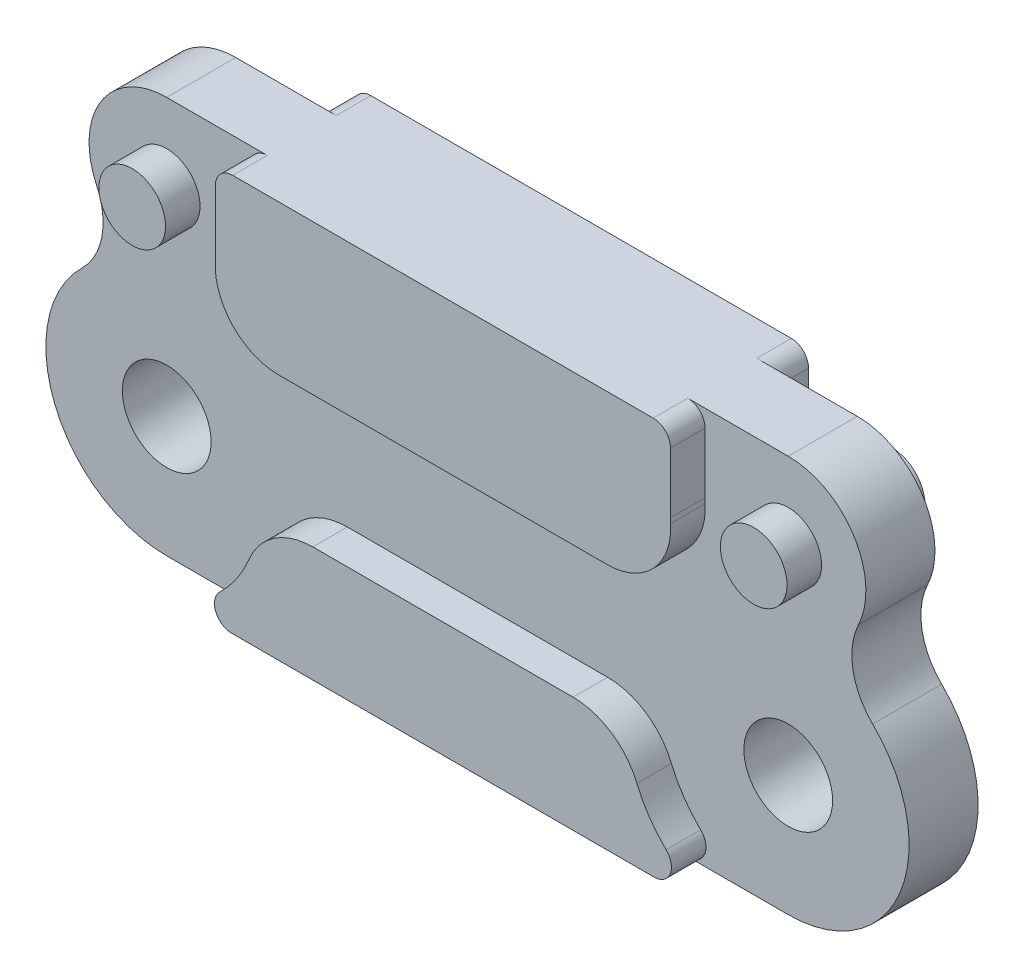
SolidWorks part; units mm, degrees
material "ABS"
ref_plane "Front Plane" through (0, 0, 0) normal (0, 0, 1) x (1, 0, 0)
ref_plane "Top Plane" through (0, 0, 0) normal (0, 1, 0) x (1, 0, 0)
ref_plane "Right Plane" through (0, 0, 0) normal (1, 0, 0) x (0, 0, -1)
sketch "Sketch1" plane through (0, 0, 0) normal (0, 0, 1) x (1, 0, 0)
  line L0 (0, 0) -> (-14.2875, 0)
  line L1 (-14.2875, 5.5563) -> (0, 5.5563)
  line L2 (0, 5.5563) -> (0, 0)
  circle A0 centre (-14.2875, 0) radius 1.7859
  circle A1 centre (-14.2875, 0) radius 5.5563
  circle A2 centre (-14.2875, 9.1281) radius 3.5719
  circle A3 centre (-14.2875, 9.1281) radius 1.7859
  circle A4 centre (-20.388, 6.2465) radius 3.175
  circle A5 centre (-7.5523, 8.7312) radius 3.175
  circle A6 centre (-1.2023, 8.7312) radius 3.175 construction
  circle A7 centre (-7.5523, 8.7312) radius 1.7859 construction
  dimension "D2" = 3.5719
  dimension "D3" = 11.1125
  dimension "D4" = 7.1437
  dimension "D5" = 6.35
  dimension "D1" = 14.2875
sketch "Sketch2" plane through (0, 0, 0) normal (0, 0, 1) x (1, 0, 0)
  line L0 (-7.5523, 11.9062) -> (7.5523, 11.9062)
  line L1 (-14.2875, -5.5563) -> (14.2875, -5.5563)
  line L2 (0, 12.7) -> (0, 15.1901) construction
  line L3 (-10.3989, -3.9688) -> (10.3989, -3.9688)
  line L4 (-14.2875, 12.7) -> (0, 12.7)
  line L5 (0, 12.7) -> (14.2875, 12.7)
  circle A0 centre (-14.2875, 0) radius 5.5563
  circle A12 centre (-14.2875, 0) radius 2.0399
  circle A14 centre (-14.2875, 0) radius 1.7859 construction
  circle A16 centre (-7.5523, 8.7312) radius 3.175
  circle A18 centre (-7.5523, 8.7312) radius 3.175 construction
  circle A19 centre (-20.388, 6.2465) radius 3.175
  circle A20 centre (-14.2875, 9.1281) radius 3.5719
  circle A21 centre (-14.2875, 9.1281) radius 3.5719 construction
  circle A23 centre (-14.2875, 0) radius 5.5563 construction
  circle A24 centre (14.2875, 9.1281) radius 3.5719
  circle A25 centre (20.388, 6.2465) radius 3.175
  circle A26 centre (7.5523, 8.7312) radius 3.175
  circle A27 centre (14.2875, 0) radius 2.0399
  circle A28 centre (14.2875, 0) radius 5.5563
  point P6 (0, 11.9062)
  point P28 (0, -5.5563)
  point P29 (0, 11.9062)
  dimension "D1" = 0.254
  dimension "D2" = 1.5875
extrude "Boss-Extrude1" add sketch "Sketch2" along normal blind 3.175 contours A0 A12 | A0 A20 | L3 L2 A20 A0 | L2 L3 | A16 | A19 | A20 | L2 L1 A28 L3 | A28 A27 | A24 | A24 A28 A25 | A26 | L2 L0 A26 A24 L5 region at (0, 12.047, 0) region at (0, 3.1015, 0) region at (-7.5523, 8.7312, 0) region at (7.5523, 8.7312, 0) region at (-14.2875, 9.1281, 0) region at (14.2875, 9.1281, 0) region at (-10.4698, 3.8177, 0) region at (-16.6309, 5.6656, 0) region at (16.6309, 5.6656, 0) region at (16.3241, 5.0002, 0) region at (0, -4.7971, 0)
sketch "Sketch4" plane through (0, 0, 3.175) normal (0, 0, 1) x (1, 0, 0)
  line L0 (-8.4828, -0.254) -> (8.4828, -0.254)
  line L1 (0, 5.5563) -> (0, 6.5431) construction
  line L2 (-14.2875, 5.8103) -> (14.2875, 5.8103)
  line L3 (0, 0) -> (-14.2875, 0) construction
  line L4 (-10.4616, 9.1281) -> (-10.4616, 12.7)
  line L5 (-14.2875, 12.7) -> (14.2875, 12.7) construction
  line L6 (-10.4616, 12.7) -> (-12.9167, 12.7)
  line L8 (10.4616, 9.1281) -> (10.4616, 12.7)
  line L9 (10.4616, 12.7) -> (12.9167, 12.7)
  circle A4 centre (-14.2875, 9.1281) radius 3.8259
  circle A5 centre (-14.2875, 9.1281) radius 1.5319
  circle A7 centre (-7.5523, 8.7312) radius 2.921
  circle A11 centre (-14.2875, 9.1281) radius 3.5719 construction
  circle A12 centre (-14.2875, 9.1281) radius 1.7859 construction
  circle A15 centre (-14.2875, 0) radius 5.8103
  circle A17 centre (-14.2875, 0) radius 5.5563 construction
  circle A24 centre (-20.388, 6.2465) radius 2.921
  circle A38 centre (14.2875, 0) radius 5.8103
  circle A39 centre (20.388, 6.2465) radius 2.921
  circle A40 centre (7.5523, 8.7312) radius 2.921
  circle A41 centre (14.2875, 9.1281) radius 1.5319
  circle A42 centre (14.2875, 9.1281) radius 3.8259
  point P38 (0, 0)
  point P49 (0, 5.8103)
  point P50 (0, -0.254)
  arc M19 (-14.2875, 12.7) -> (-17.5172, 7.6025) centre (-14.2875, 9.1281) ccw
  arc M21 (-18.1697, 3.975) -> (-14.2875, -5.5563) centre (-14.2875, 0) ccw
  line M22 (-14.2875, -5.5563) -> (14.2875, -5.5563)
  circle M38 centre (-14.2875, 0) radius 2.0399
  arc M44 (-17.5172, 7.6025) -> (-18.1697, 3.975) centre (-20.388, 6.2465) cw
  line M72 (14.2875, 12.7) -> (-14.2875, 12.7)
  arc M74 (14.2875, -5.5563) -> (18.1697, 3.975) centre (14.2875, 0) ccw
  arc M75 (17.5172, 7.6025) -> (14.2875, 12.7) centre (14.2875, 9.1281) ccw
  arc M78 (18.1697, 3.975) -> (17.5172, 7.6025) centre (20.388, 6.2465) cw
  circle M79 centre (14.2875, 0) radius 2.0399
  dimension "D1" = 0.254
  dimension "D2" = 0.254
  dimension "D3" = 0.254
  dimension "D4" = 0.254
extrude "Cut-Extrude2" cut sketch "Sketch4" against normal blind 1.5875 contours A4 A15 M44 M21 M22 M38 | L0 L1 L2 A4 A15 | L1 L0 A38 A42 L2 | A38 A42 M22 M74 M78 M79 | A42 A38 M78 | A42 L2 A38 A41 M78 M75 M72 | L2 A42 A40 | A7 A4 L2 | A15 L2 A4 A5 M72 M19 M44 | A15 A4 M44 | A4 A15 | A15 A4 L2 | A42 A38 L2 | A42 A38 | L8 A42 M72 | A4 L4 M72 region at (0, 2.9857, 3.175) region at (-9.8194, -3.4596, 3.175) region at (9.7293, 3.34, 3.175) region at (13.0052, 5.7483, 3.175) region at (14.2875, 5.5668, 3.175) region at (-13.0052, 5.7483, 3.175) region at (-14.2875, 5.5668, 3.175) region at (13.335, 5.9127, 3.175) region at (10.4134, 6.5196, 3.175) region at (16.8395, 5.6933, 3.175) region at (-16.8395, 5.6933, 3.175) region at (-16.5242, 6.1514, 3.175) region at (-10.4134, 6.5196, 3.175) region at (-11.127, 11.8735, 3.175) region at (11.127, 11.8735, 3.175)
fillet "Fillet2" radius 3.175 2 edges at (8.4828, -0.254, 2.3812) (-8.4828, -0.254, 2.3812)
fillet "Fillet6" radius 0.7937 4 edges at (12.5884, -5.5563, 2.3812) (-12.5884, -5.5563, 2.3812) (10.4616, 12.7, 2.3812) (-10.4616, 12.7, 2.3812)
mirror "Mirror2" about plane through (0, 0, 0) normal (0, 0, 1) of "Cut-Extrude2", "Boss-Extrude1", "Fillet2", "Fillet6"
